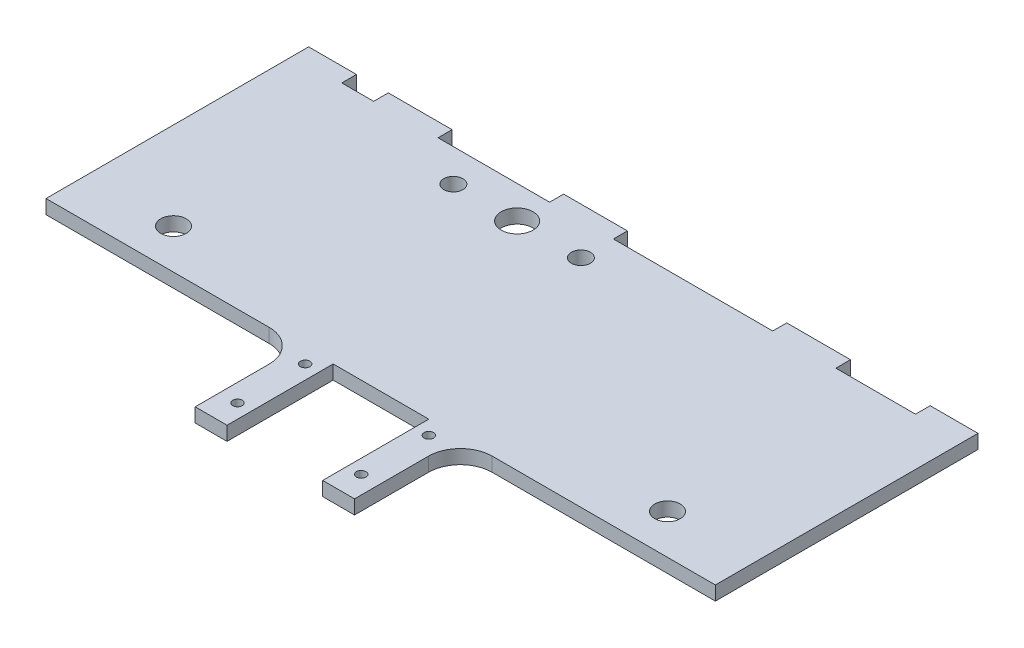
SolidWorks part; units mm, degrees
ref_plane "Front Plane" through (0, 0, 0) normal (0, 0, 1) x (1, 0, 0)
ref_plane "Top Plane" through (0, 0, 0) normal (0, 1, 0) x (1, 0, 0)
ref_plane "Right Plane" through (0, 0, 0) normal (1, 0, 0) x (0, 0, -1)
sketch "Sketch1" plane through (0, 0, 0) normal (0, 1, 0) x (1, 0, 0)
  line L0 (12.7, 98.806) -> (279.4, 98.806) construction
  line L3 (12.7, 104.648) -> (31.75, 104.648)
  line L5 (31.75, 104.648) -> (31.75, 98.806)
  line L6 (31.75, 98.806) -> (44.45, 98.806)
  line L7 (12.7, 0) -> (279.4, 0) construction
  line L8 (44.45, 98.806) -> (44.45, 104.648)
  line L10 (114.3, -42.164) -> (127, -42.164)
  line L12 (146.05, 0.1228) -> (165.1, 0.1228)
  line L13 (165.1, 0.1228) -> (165.1, -42.164)
  line L14 (146.05, 0.1228) -> (127, 0.1228)
  line L15 (127, 0.1228) -> (127, -42.164)
  line L16 (165.1, -42.164) -> (177.8, -42.164)
  line L17 (12.7, 0) -> (101.6, 0)
  line L18 (114.3, -12.7) -> (114.3, -42.164)
  line L19 (279.4, 0) -> (190.5, 0)
  line L20 (177.8, -12.7) -> (177.8, -42.164)
  line L27 (114.3, 104.648) -> (139.7, 104.648)
  line L28 (203.2, 104.648) -> (228.6, 104.648)
  line L29 (69.85, 104.648) -> (69.85, 99.06)
  line L30 (69.85, 99.06) -> (114.3, 99.06)
  line L31 (114.3, 99.06) -> (114.3, 104.648)
  line L32 (139.7, 104.648) -> (139.7, 99.06)
  line L33 (139.7, 99.06) -> (203.2, 99.06)
  line L34 (203.2, 99.06) -> (203.2, 104.648)
  line L35 (228.6, 104.648) -> (228.6, 98.806)
  line L36 (228.6, 98.806) -> (260.35, 98.806)
  line L37 (260.35, 98.806) -> (260.35, 104.648)
  line L38 (44.45, 104.648) -> (69.85, 104.648)
  line L39 (260.35, 104.648) -> (279.4, 104.648)
  line L40 (279.4, 104.648) -> (279.4, 0)
  line L41 (12.7, 104.648) -> (12.7, 0)
  arc A0 (190.5, 0) -> (177.8, -12.7) centre (190.5, -12.7) ccw
  arc A1 (114.3, -12.7) -> (101.6, 0) centre (101.6, -12.7) ccw
  point P0 (0, 0)
  point P10 (0, -41.181)
  point P27 (95.25, 0)
  dimension "D6" = 12.7
  dimension "D2" = 19.05
  dimension "D3" = 5.842
  dimension "D4" = 98.806
  dimension "D5" = 19.05
  dimension "D7" = 12.7
  dimension "D8" = 63.5
  dimension "D9" = 19.05
  dimension "D10" = 25.4
  dimension "D11" = 5.588
  dimension "D12" = 25.4
  dimension "D13" = 29.464
  dimension "D14" = 42.2868
  dimension "D15" = 12.7
  dimension "D16" = 44.45
  dimension "D17" = 25.4
  dimension "D18" = 31.75
extrude "Boss-Extrude1" add sketch "Sketch1" along normal blind 5.588
sketch "Sketch5" plane through (0, 5.588, 0) normal (0, 1, 0) x (1, 0, 0)
  line L1 (190.5, 0) -> (279.4, 0) construction
  line L3 (12.7, 0) -> (101.6, 0) construction
  line L4 (127, -42.164) -> (127, 0.1228) construction
  line L6 (165.1, 0.1228) -> (165.1, -42.164) construction
  circle A0 centre (244.475, 15.8708) radius 5.08
  circle A1 centre (47.625, 15.8708) radius 5.08
  dimension "D1" = 10.16
  dimension "D2" = 10.16
  dimension "D3" = 79.375
  dimension "D4" = 15.8708
  dimension "D5" = 79.375
  dimension "D6" = 15.8708
extrude "Cut-Extrude1" cut sketch "Sketch5" against normal up to next
sketch "Sketch6" plane through (0, 0, 0) normal (0, -1, 0) x (1, 0, 0)
  line L0 (12.7, -104.648) -> (12.7, 0) construction
  line L1 (44.45, -98.806) -> (31.75, -98.806) construction
  circle A0 centre (114.3, -86.106) radius 6.35
  dimension "D1" = 12.7
  dimension "D2" = 101.6
  dimension "D3" = 12.7
extrude "Cut-Extrude2" cut sketch "Sketch6" against normal up to next
sketch "Sketch7" plane through (0, 5.588, 0) normal (0, 1, 0) x (1, 0, 0)
  circle A0 centre (139.7, 86.106) radius 3.81
  circle A1 centre (114.3, 86.106) radius 6.35 construction
  circle A2 centre (88.9, 86.106) radius 3.81
  point P2 (0, 0)
  dimension "D1" = 7.62
  dimension "D4" = 7.62
  dimension "D5" = 0
  dimension "D2" = 25.4
  dimension "D3" = 25.4
extrude "Cut-Extrude3" cut sketch "Sketch7" against normal up to next
sketch "Sketch10" plane through (0, 5.588, 0) normal (0, 1, 0) x (1, 0, 0)
  point P0 (170.688, -5.4568)
  point P1 (170.688, -32.3976)
  point P3 (121.412, -5.4568)
  point P5 (121.412, -32.3976)
hole_wizard "#6 Clearance Hole1" positions "Sketch11" profile "Sketch12" hole size "#6" standard "ANSI Inch" end condition through all
sketch "Sketch11" plane through (0, 5.588, 0) normal (0, 1, 0) x (1, 0, 0)
  point P0 (121.412, -5.4568)
  point P3 (121.412, -32.3976)
  point P6 (170.688, -32.3976)
  point P9 (170.688, -5.4568)
sketch "Sketch12" plane through (121.412, 5.588, 5.4568) normal (1, 0, 0) x (0, 0, 1)
  line L0 (0, 0) -> (0, 5.588)
  line L1 (0, 5.588) -> (1.8986, 5.588)
  line L2 (1.8986, 5.588) -> (1.8986, 0)
  line L5 (1.8986, 0) -> (0, 0)
  line L11 (0, -6.35) -> (0, 107.95) construction
  dimension "Thru Hole Dia." = 3.7973
  dimension "Thru Hole Depth" = 5.588
